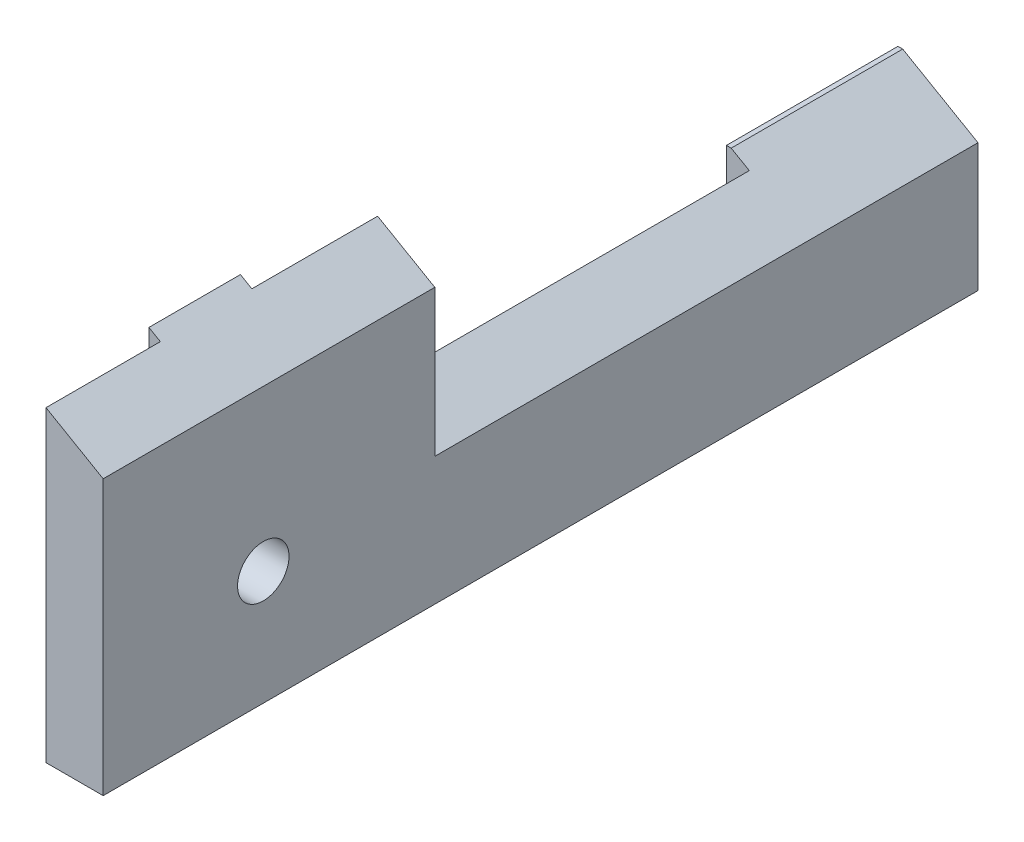
SolidWorks part; units mm, degrees
material "3D printed plastic"
ref_plane "Front Plane" through (0, 0, 0) normal (0, 0, 1) x (1, 0, 0)
ref_plane "Top Plane" through (0, 0, 0) normal (0, 1, 0) x (1, 0, 0)
ref_plane "Right Plane" through (0, 0, 0) normal (1, 0, 0) x (0, 0, -1)
sketch "Sketch1" plane through (0, 0, 0) normal (0, 1, 0) x (1, 0, 0)
  line L0 (-5, -20.25) -> (-5, 23.25)
  line L1 (0, 38.25) -> (-7, 38.25)
  line L2 (0, 38.25) -> (0, -38.25)
  line L3 (0, -38.25) -> (-5, -38.25)
  line L4 (-7, 38.25) -> (-7, 23.25)
  line L5 (-5, -20.25) -> (-6, -20.25)
  line L6 (-6, -24.25) -> (0, -24.25) construction
  line L7 (-7, 23.25) -> (-5, 23.25)
  line L8 (-5, -38.25) -> (-5, -28.25)
  line L9 (-5, -28.25) -> (-6, -28.25)
  line L10 (-6, -20.25) -> (-6, -28.25)
  dimension "D1" = 62.5
  dimension "D2" = 15
  dimension "D3" = 2
  dimension "D4" = 5
  dimension "D5" = 8
  dimension "D6" = 14
  dimension "D7" = 1
extrude "Boss-Extrude1" add sketch "Sketch1" along normal mid plane 28
sketch "Sketch2" plane through (0, 0, 0) normal (1, 0, 0) x (0, 0, -1)
  line L0 (-24.25, -4) -> (-24.25, 14) construction
  line L1 (-38.25, 14) -> (38.25, 14) construction
  line L2 (-20.25, 14) -> (-28.25, 14) construction
  line L5 (-38.25, -14) -> (38.25, -14) construction
  line L7 (-24.25, -14) -> (-24.25, -4) construction
  circle A0 centre (-24.25, -4) radius 2.25
  dimension "D2" = 4.5
  dimension "D1" = 10
extrude "Cut-Extrude1" cut sketch "Sketch2" against normal through all
sketch "Sketch4" plane through (0, 0, 0) normal (1, 0, 0) x (0, 0, -1)
  line L0 (23.25, 14) -> (-20.25, 14) construction
  line L1 (-9.25, 14) -> (38.25, 14)
  line L2 (-9.25, 14) -> (-9.25, 1)
  line L3 (-9.25, 1) -> (38.25, 1)
  line L4 (38.25, 14) -> (38.25, 1)
  line L5 (38.25, 14) -> (38.25, -14) construction
  line L6 (38.25, -14) -> (23.25, -14) construction
  circle A0 centre (-24.25, -4) radius 2.25 construction
  dimension "D1" = 15
  dimension "D2" = 15
extrude "Cut-Extrude3" cut sketch "Sketch4" against normal through all
chamfer "Chamfer1" distance 4 angle 60 1 edges at (0, 14, 23.75) first distance on face at (0, -4, 22)
chamfer "Chamfer2" distance 3.8 angle 60 1 edges at (0, 1, -14.5) first distance on face at (0, -4, 22)
